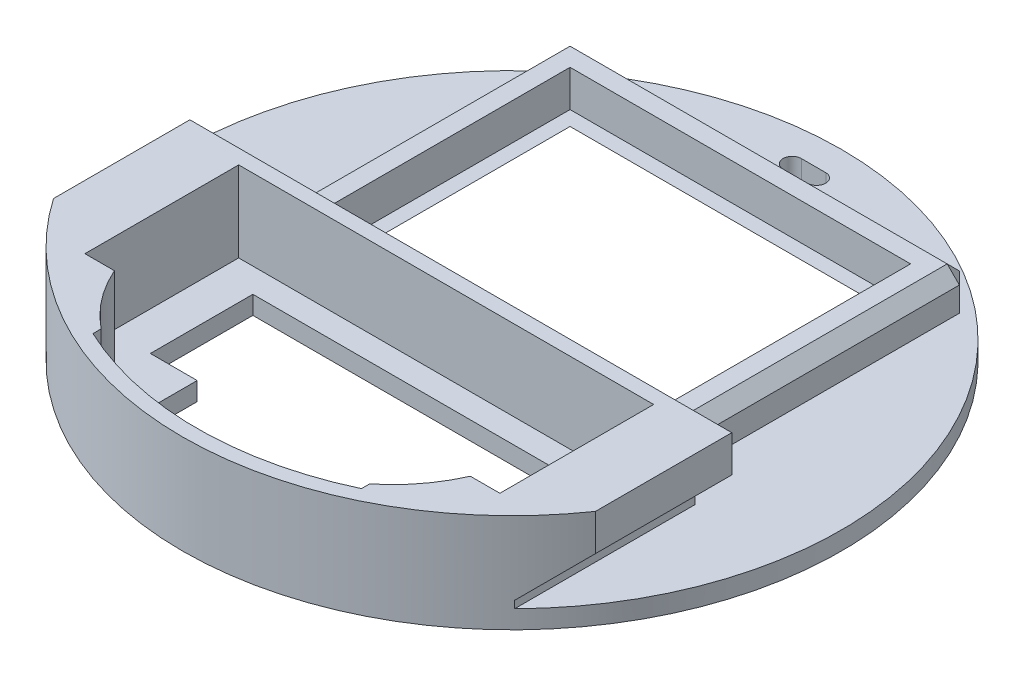
SolidWorks part; units mm, degrees
note: The reader was unsure of these and kept them because the rebuilt part matched: shared geometry of "Sketch1<3>", "Sketch1<5>".
ref_plane "Front Plane" through (0, 0, 0) normal (0, 0, 1) x (1, 0, 0)
ref_plane "Top Plane" through (0, 0, 0) normal (0, 1, 0) x (1, 0, 0)
ref_plane "Right Plane" through (0, 0, 0) normal (1, 0, 0) x (0, 0, -1)
sketch "Sketch1" plane through (0, 0, 0) normal (0, 1, 0) x (1, 0, 0)
  line L0 (-16.8, 1.5) -> (16.8, 1.5) construction
  line L1 (-16.8, -6.1) -> (16.8, -6.1) construction
  line L2 (-16.8, -6.1) -> (-16.8, 6.1) construction
  line L3 (-16.8, 6.1) -> (16.8, 6.1) construction
  line L4 (16.8, -6.1) -> (16.8, 6.1) construction
  line L5 (-16.8, -6.1) -> (16.8, 6.1) construction
  line L6 (-16.8, 6.1) -> (16.8, -6.1) construction
  line L7 (0, 0) -> (0, -4) construction
  line L8 (-5, -5.4) -> (5, -5.4) construction
  line L9 (-5, -5.4) -> (-5, -2.6) construction
  line L10 (-5, -2.6) -> (5, -2.6) construction
  line L11 (5, -5.4) -> (5, -2.6) construction
  line L12 (-5, -5.4) -> (5, -2.6) construction
  line L13 (-5, -2.6) -> (5, -5.4) construction
  line L14 (0, 0) -> (0, 35.65) construction
  line L15 (-13.8189, -11.5) -> (13.8189, -11.5) construction
  line L16 (-12.75, 7.1) -> (12.75, 7.1) construction
  line L17 (-12.75, 7.1) -> (-12.75, 33.2) construction
  line L18 (-12.75, 33.2) -> (12.75, 33.2) construction
  line L19 (12.75, 7.1) -> (12.75, 33.2) construction
  line L20 (-12.75, 7.1) -> (12.75, 33.2) construction
  line L21 (-12.75, 33.2) -> (12.75, 7.1) construction
  line L22 (-12.75, 12.2) -> (12.75, 12.2)
  line L23 (-12.75, 12.2) -> (-12.75, 29.2)
  line L24 (-12.75, 29.2) -> (12.75, 29.2)
  line L25 (12.75, 12.2) -> (12.75, 29.2)
  line L26 (-12.75, 12.2) -> (12.75, 29.2) construction
  line L27 (-12.75, 29.2) -> (12.75, 12.2) construction
  line L29 (-4.5, -3.6738) -> (-4.5, 4.3) construction
  line L30 (-3.5, 5.3) -> (3.5, 5.3) construction
  line L31 (4.5, -3.6738) -> (4.5, 4.3) construction
  line L32 (-15.6377, 4.3) -> (-15.6377, -1.291) construction
  line L33 (-13.8377, 6.1) -> (-7.8377, 6.1) construction
  line L35 (6.8377, -3.6738) -> (6.8377, 4.3) construction
  line L36 (7.8377, 5.3) -> (13.8377, 5.3) construction
  line L37 (14.8377, -1.291) -> (14.8377, 4.3) construction
  line L38 (6.8377, -3.6738) -> (14.8377, 5.3) construction
  line L39 (6.8377, 5.3) -> (14.8377, -1.291) construction
  line L41 (-14.8377, -1.291) -> (-14.8377, 4.3) construction
  line L42 (-13.8377, 5.3) -> (-7.8377, 5.3) construction
  line L43 (-6.8377, -3.6738) -> (-6.8377, 4.3) construction
  line L44 (-14.8377, -1.291) -> (-6.8377, 5.3) construction
  line L45 (-14.8377, 5.3) -> (-6.8377, -3.6738) construction
  line L46 (-2.8, -11.5) -> (-2, -11.5) construction
  line L47 (-5.1594, -3.6738) -> (-5.1594, 4.3) construction
  line L48 (-3.3594, 6.1) -> (3.3594, 6.1) construction
  line L49 (5.1594, -3.6738) -> (5.1594, 4.3) construction
  line L50 (2.8, -11.5) -> (2, -11.5) construction
  line L51 (-6.0377, 4.3) -> (-6.0377, -3.6738) construction
  line L52 (15.6377, -1.291) -> (15.6377, 4.3) construction
  line L53 (13.8377, 6.1) -> (7.8377, 6.1) construction
  line L54 (6.0377, 4.3) -> (6.0377, -3.6738) construction
  line L55 (-8.7689, -11.5) -> (-8.7689, -12.4022) construction
  line L56 (-4.7689, -11.5) -> (-3.8406, -11.5) construction
  line L57 (3.8406, -11.5) -> (4.7689, -11.5) construction
  line L58 (8.7689, -11.5) -> (8.7689, -12.4022) construction
  line L59 (-4.5, -3.6738) -> (4.5, -3.6738) construction
  line L60 (-12.75, 20.7) -> (12.75, 20.7) construction
  line L61 (-17, 6.3) -> (17, 6.3)
  line L62 (-17, 6.3) -> (-17, -6.3)
  line L64 (17, 6.3) -> (17, -6.3)
  line L65 (-22.2, 7.5) -> (22.2, 7.5)
  line L66 (-22.2, 7.5) -> (-22.2, -3.6719)
  line L68 (22.2, 7.5) -> (22.2, -3.6719)
  line L69 (-13.95, 30.4) -> (13.95, 30.4)
  line L70 (-13.95, 30.4) -> (-13.95, 11)
  line L71 (-13.95, 11) -> (13.95, 11)
  line L72 (13.95, 30.4) -> (13.95, 11)
  line L75 (-10, -12.0875) -> (-10, -4.1)
  line L77 (-13.8377, -4.1) -> (-10, -4.1)
  line L78 (-13.8377, -4.1) -> (-13.8377, 4.3)
  line L79 (-13.8377, 4.3) -> (13.8377, 4.3)
  line L80 (13.8377, -4.1) -> (13.8377, 4.3)
  line L81 (10, -12.0875) -> (10, -4.1)
  line L82 (-17, -6.3) -> (-14.5829, -6.3)
  line L83 (10, -4.1) -> (13.8377, -4.1)
  line L84 (-11, -10.971) -> (-11, -11.6419)
  line L85 (17, -6.3) -> (14.5829, -6.3)
  line L87 (11, -10.971) -> (11, -11.6419)
  line L88 (-1, 35.65) -> (1, 35.65) construction
  line L89 (-16.45, 32.9) -> (16.45, 32.9)
  line L90 (-16.45, 32.9) -> (-16.45, 7.5)
  line L91 (-16.45, 7.5) -> (16.45, 7.5)
  line L92 (16.45, 32.9) -> (16.45, 7.5)
  line L95 (-1, 36.4) -> (1, 36.4)
  line L96 (-1, 34.9) -> (1, 34.9)
  circle A0 centre (11.45, 1.5) radius 2.5 construction
  circle A1 centre (0, 1.5) radius 2.5 construction
  circle A2 centre (-11.45, 1.5) radius 2.5 construction
  circle A3 centre (0, 11.6956) radius 25 construction
  circle A4 centre (0, 11.6956) radius 27
  arc A5 (-14.8377, -1.291) -> (-8.7689, -11.5) centre (-3.2164, -1.291) ccw construction
  arc A6 (-6.8377, -3.6738) -> (-4.7689, -11.5) centre (9, -3.6738) ccw construction
  arc A7 (4.5, -3.6738) -> (2, -11.5) centre (-9, -3.6738) cw construction
  arc A8 (-4.5, -3.6738) -> (-2, -11.5) centre (9, -3.6738) ccw construction
  arc A9 (6.8377, -3.6738) -> (4.7689, -11.5) centre (-9, -3.6738) cw construction
  arc A10 (14.8377, -1.291) -> (8.7689, -11.5) centre (3.2164, -1.291) cw construction
  arc A11 (4.5, 4.3) -> (3.5, 5.3) centre (3.5, 4.3) ccw construction
  arc A12 (-3.5, 5.3) -> (-4.5, 4.3) centre (-3.5, 4.3) ccw construction
  arc A13 (-2.8, -11.5) -> (-5.1594, -3.6738) centre (9, -3.6738) cw construction
  arc A14 (-3.3594, 6.1) -> (-5.1594, 4.3) centre (-3.3594, 4.3) ccw construction
  arc A15 (3.3594, 6.1) -> (5.1594, 4.3) centre (3.3594, 4.3) cw construction
  arc A16 (2.8, -11.5) -> (5.1594, -3.6738) centre (-9, -3.6738) ccw construction
  arc A17 (-15.6377, -1.291) -> (-8.7689, -12.4022) centre (-3.2164, -1.291) ccw construction
  arc A18 (-6.0377, -3.6738) -> (-3.8406, -11.5) centre (9, -3.6738) ccw construction
  arc A19 (6.0377, -3.6738) -> (3.8406, -11.5) centre (-9, -3.6738) cw construction
  arc A20 (15.6377, -1.291) -> (8.7689, -12.4022) centre (3.2164, -1.291) cw construction
  arc A21 (-6.8377, 4.3) -> (-7.8377, 5.3) centre (-7.8377, 4.3) ccw construction
  arc A22 (-13.8377, 5.3) -> (-14.8377, 4.3) centre (-13.8377, 4.3) ccw construction
  arc A23 (15.6377, 4.3) -> (13.8377, 6.1) centre (13.8377, 4.3) ccw construction
  arc A24 (7.8377, 6.1) -> (6.0377, 4.3) centre (7.8377, 4.3) ccw construction
  arc A25 (-6.0377, 4.3) -> (-7.8377, 6.1) centre (-7.8377, 4.3) ccw construction
  arc A26 (-13.8377, 6.1) -> (-15.6377, 4.3) centre (-13.8377, 4.3) ccw construction
  arc A27 (14.8377, 4.3) -> (13.8377, 5.3) centre (13.8377, 4.3) ccw construction
  arc A28 (7.8377, 5.3) -> (6.8377, 4.3) centre (7.8377, 4.3) ccw construction
  arc A35 (-11, -11.6419) -> (11, -11.6419) centre (0, 11.6956) ccw
  arc A36 (-14.5829, -6.3) -> (-11, -10.971) centre (-3.2164, -1.291) ccw
  arc A37 (14.5829, -6.3) -> (11, -10.971) centre (3.2164, -1.291) cw
  arc A40 (-1, 36.4) -> (-1, 34.9) centre (-1, 35.65) ccw
  arc A41 (1, 34.9) -> (1, 36.4) centre (1, 35.65) ccw
  point P0 (0, 0)
  point P16 (0, -4)
  point P21 (0, 20.15)
  point P29 (0, 20.7)
  point P66 (0, 6.1)
  point P148 (0, 35.65)
  dimension "D6" = 28.25
  dimension "D7" = 5
  dimension "D11" = 50
  dimension "D18" = 54
  dimension "D19" = 18
  dimension "D20" = 4
  dimension "D21" = 1
  dimension "D24" = 1.8
  dimension "D36" = 1
  dimension "D40" = 1.8
  dimension "D41" = 1
  dimension "D30" = 1.2
  dimension "D1" = 12.2
  dimension "D2" = 33.6
  dimension "D3" = 4.6
  dimension "D4" = 5.35
  dimension "D5" = 16.8
  dimension "D8" = 10
  dimension "D9" = 3.5
  dimension "D10" = 0.7
  dimension "D12" = 26.1
  dimension "D13" = 25.5
  dimension "D14" = 1
  dimension "D15" = 4
  dimension "D16" = 17
  dimension "D17" = 13
  dimension "D22" = 0.8
  dimension "D23" = 0.8
  dimension "D25" = 9
  dimension "D26" = 8
  dimension "D27" = 0.2
  dimension "D28" = 0.2
  dimension "D29" = 8
  dimension "D31" = 4
  dimension "D32" = 4
  dimension "D33" = 0.8
  dimension "D34" = 0.8
  dimension "D35" = 0.8
  dimension "D37" = 0.8
  dimension "D38" = 0.8
  dimension "D39" = 0.8
  dimension "D42" = 44.4
  dimension "D43" = 1.2
  dimension "D44" = 2
  dimension "D45" = 1.2
  dimension "D46" = 1.2
  dimension "D47" = 0.2
  dimension "D48" = 7
  dimension "D49" = 6
  dimension "D50" = 2.5
  dimension "D51" = 2.5
  dimension "D52" = 2
  dimension "D53" = 1.5
  dimension "D54" = 2
extrude "Boss-Extrude1" add sketch "Sketch1" against normal blind 1.5 contours L72 L69 L70 L71 L25 L22 L23 L24 | L92 L89 L90 L91 L69 L72 L71 L70 | L68 A4 L66 L65 L89 L92 L91 L90 | L66 A4 L68 L65 L85 A37 L87 A35 L84 A36 L82 L62 L61 L64 | A37 L85 L64 L61 L62 L82 A36 L84 A35 L75 L77 L78 L79 L80 L83 L81 L87
extrude "Boss-Extrude2" add sketch "Sketch1<3>" along normal blind 6.6
sketch "Sketch1<3>" plane through (0, 0, 0) normal (0, 1, 0) x (1, 0, 0) same geometry as "Sketch1"
sketch "Sketch2" plane through (0, 0, -6.3) normal (0, 0, 1) x (1, 0, 0)
  line L0 (-22.2, 3.6) -> (-19.2, 0.6)
  line L1 (-22.2, 6.6) -> (-22.2, 0) construction
  line L2 (-19.2, 0.6) -> (-19.2, 0)
  line L3 (-19.2, 0) -> (-22.2, 0)
  line L4 (0, 0) -> (0, 16.7972) construction
  line L5 (-22.2, 3.6) -> (-22.2, 0)
  line L6 (19.2, 0.6) -> (19.2, 0)
  line L7 (22.2, 3.6) -> (22.2, 0)
  line L8 (22.2, 3.6) -> (19.2, 0.6)
  line L9 (19.2, 0) -> (22.2, 0)
  line L10 (22.2, 6.6) -> (-22.2, 6.6) construction
  dimension "D1" = 45
  dimension "D2" = 0.6
  dimension "D3" = 3
  dimension "D4" = 3
extrude "Cut-Extrude1" cut sketch "Sketch2" along normal up to next and the other way up to next (1.2 mm away) contours L5 L3 L2 L0 | L6 L9 L7 L8
extrude "Boss-Extrude3" add sketch "Sketch1<5>" along normal blind 3 contours L92 L89 L90 L91 L69 L72 L71 L70
sketch "Sketch1<5>" plane through (0, 0, 0) normal (0, 1, 0) x (1, 0, 0) same geometry as "Sketch1"
chamfer "Chamfer1" distance 1.5 angle 45 4 edges at (-12.75, -1.5, -20.7) (0, -1.5, -12.2) (0, -1.5, -29.2) (12.75, -1.5, -20.7)
chamfer "Chamfer2" distance 1 angle 45 8 edges at (-16.45, 1.5, -7.5) (0, 3, -7.5) (16.45, 1.5, -7.5) (-16.45, 1.5, -32.9) (16.45, 1.5, -32.9) (-16.45, 3, -20.2) (0, 3, -32.9) (16.45, 3, -20.2)
